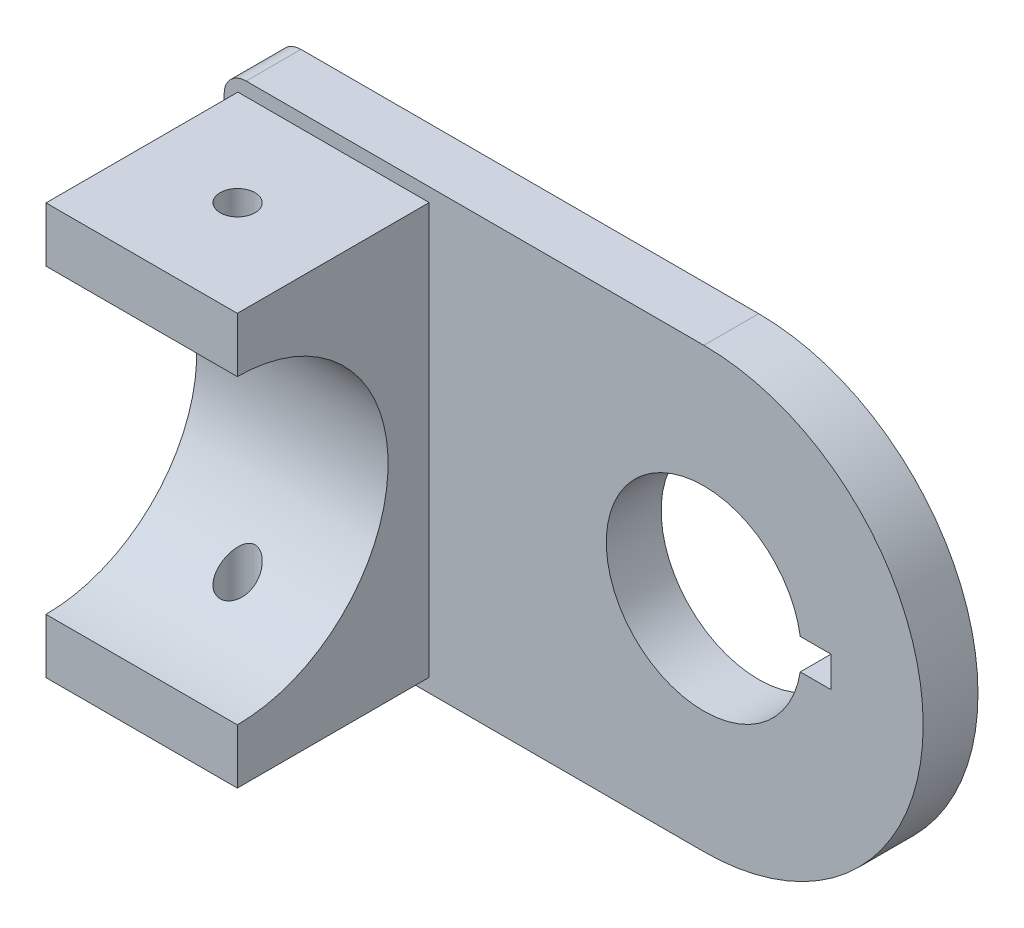
SolidWorks part; units mm, degrees
ref_plane "Front Plane" through (0, 0, 0) normal (0, 0, 1) x (1, 0, 0)
ref_plane "Top Plane" through (0, 0, 0) normal (0, 1, 0) x (1, 0, 0)
ref_plane "Right Plane" through (0, 0, 0) normal (1, 0, 0) x (0, 0, -1)
sketch "Sketch1" plane through (0, 0, 0) normal (0, 0, 1) x (1, 0, 0)
  line L0 (66.7248, 27.178) -> (70.2808, 27.178)
  line L1 (2.54, 0) -> (55.5625, 0)
  line L2 (0, 2.54) -> (0, 48.26)
  line L3 (2.54, 50.8) -> (55.5625, 50.8)
  line L5 (70.2808, 27.178) -> (70.2808, 23.622)
  line L6 (70.2808, 23.622) -> (66.7248, 23.622)
  line L7 (55.5625, 25.4) -> (73.7816, 25.4) construction
  arc A0 (55.5625, 0) -> (55.5625, 50.8) centre (55.5625, 25.4) ccw
  arc A1 (66.7248, 27.178) -> (66.7248, 23.622) centre (55.5625, 25.4) ccw
  arc A2 (2.54, 0) -> (0, 2.54) centre (2.54, 2.54) cw
  arc A3 (2.54, 50.8) -> (0, 48.26) centre (2.54, 48.26) ccw
  point P9 (64.6721, 25.4)
  point P14 (0, 0)
  point P17 (0, 50.8)
  dimension "D3" = 25.4
  dimension "D4" = 25.4
  dimension "D5" = 22.606
  dimension "D9" = 2.54
  dimension "D1" = 55.5625
  dimension "D2" = 50.8
  dimension "D6" = 1.778
  dimension "D7" = 1.778
  dimension "D8" = 3.556
extrude "Boss-Extrude1" add sketch "Sketch1" along normal blind 6.35
sketch "Sketch2" plane through (0, 0, 6.35) normal (0, 0, 1) x (1, 0, 0)
  line L0 (2.54, 0) -> (55.5625, 0) construction
  line L1 (1.5875, 1.5875) -> (23.749, 1.5875)
  line L2 (1.5875, 1.5875) -> (1.5875, 49.2125)
  line L3 (1.5875, 49.2125) -> (23.749, 49.2125)
  line L4 (23.749, 1.5875) -> (23.749, 49.2125)
  line L6 (0, 48.26) -> (0, 2.54) construction
  dimension "D1" = 22.1615
  dimension "D2" = 47.625
  dimension "D3" = 1.5875
  dimension "D4" = 1.5875
extrude "Boss-Extrude2" add sketch "Sketch2" along normal blind 22.225
sketch "Sketch3" plane through (1.5875, 0, 0) normal (-1, 0, 0) x (0, 0, 1)
  line L2 (28.575, 49.2125) -> (28.575, 1.5875) construction
  line L3 (28.575, 1.5875) -> (6.35, 1.5875) construction
  arc A1 (28.575, 7.9375) -> (28.575, 42.8625) centre (28.575, 25.4) cw
  dimension "D1" = 6.35
extrude "Cut-Extrude1" cut sketch "Sketch3" against normal blind 57.531 and the other way through all flip side to cut
hole_wizard "#10-32 Tapped Hole1" positions "Sketch7" profile "Sketch6" tap size "#10-32" standard "ANSI Inch" end condition up to next
sketch "Sketch7" plane through (0, 49.2125, 0) normal (0, 1, 0) x (1, 0, 0)
  line L0 (12.6682, -6.35) -> (12.6683, -28.575) construction
  line L1 (23.749, -6.35) -> (1.5875, -6.35) construction
  line L2 (23.749, -28.575) -> (1.5875, -28.575) construction
  line L4 (1.5875, -17.4625) -> (23.749, -17.4625) construction
  line L5 (1.5875, -28.575) -> (1.5875, -6.35) construction
  line L6 (23.749, -28.575) -> (23.749, -6.35) construction
  point P0 (12.6683, -17.4625)
  point P34 (11.0808, -17.4625)
sketch "Sketch6" plane through (12.6683, 49.2125, 17.4625) normal (1, 0, 0) x (0, 0, 1)
  line L0 (0, 0) -> (0, 10.3421)
  line L1 (0, 10.3421) -> (2.0193, 10.3421)
  line L2 (2.0193, 10.3421) -> (2.0193, 0)
  line L5 (2.0193, 0) -> (0, 0)
  line L11 (0, -6.35) -> (0, 107.95) construction
  dimension "Thru Tap Drill Dia." = 4.0386
  dimension "Thru Tap Drill Depth" = 10.3421
cosmetic thread "Hole Thread1" parameters "D2"=4.826
hole_wizard "#10-32 Tapped Hole2" positions "Sketch8" profile "Sketch9" tap size "#10-32" standard "ANSI Inch" end condition up to next
sketch "Sketch8" plane through (0, 1.5875, 0) normal (0, -1, 0) x (-1, 0, 0)
  point P22 (-12.6683, -17.4625)
sketch "Sketch9" plane through (12.6683, 1.5875, 17.4625) normal (1, 0, 0) x (0, 0, -1)
  line L0 (0, 0) -> (0, 10.3421)
  line L1 (0, 10.3421) -> (2.0193, 10.3421)
  line L2 (2.0193, 10.3421) -> (2.0193, 0)
  line L5 (2.0193, 0) -> (0, 0)
  line L11 (0, -6.35) -> (0, 107.95) construction
  dimension "Thru Tap Drill Dia." = 4.0386
  dimension "Thru Tap Drill Depth" = 10.3421
cosmetic thread "Hole Thread2" parameters "D2"=4.826
